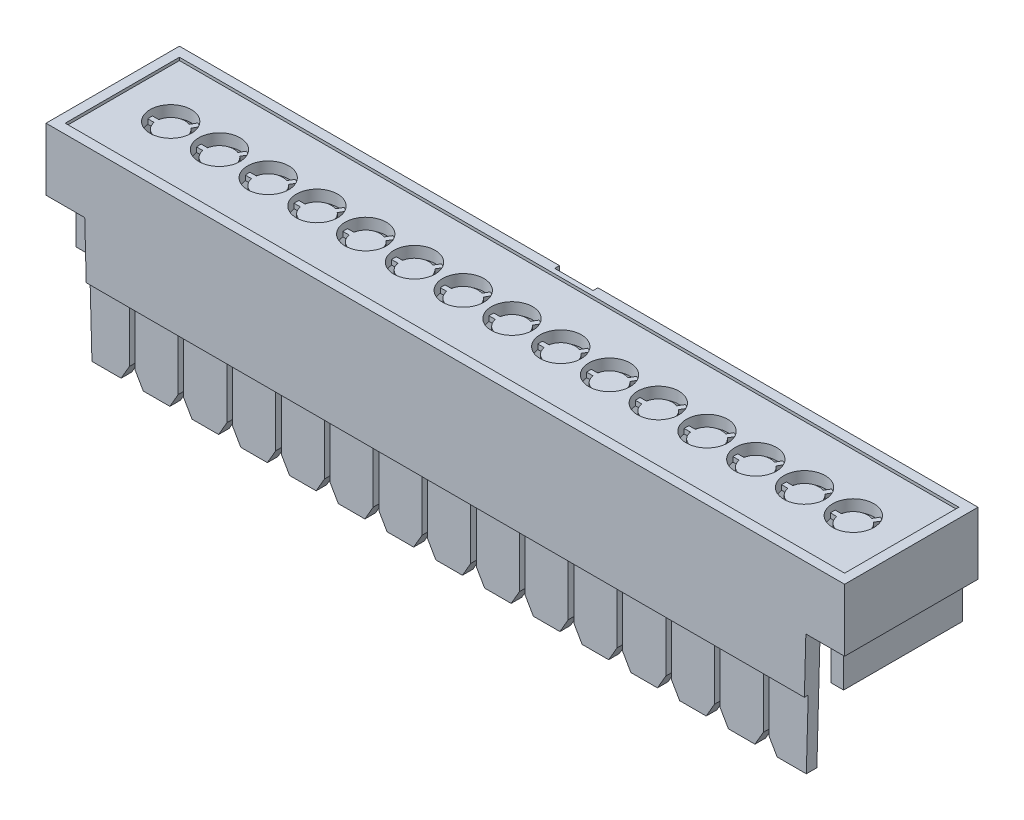
SolidWorks part; units mm, degrees
ref_plane "Спереди" through (0, 0, 0) normal (0, 0, 1) x (1, 0, 0)
ref_plane "Сверху" through (0, 0, 0) normal (0, 1, 0) x (1, 0, 0)
ref_plane "Справа" through (0, 0, 0) normal (1, 0, 0) x (0, 0, -1)
sketch "Эскиз1" plane through (0, 0, 0) normal (0, 1, 0) x (1, 0, 0)
  line L1 (41.6, -6.95) -> (-41.6, -6.95)
  line L2 (41.6, -6.95) -> (41.6, 6.95)
  line L3 (41.6, 6.95) -> (-41.6, 6.95)
  line L4 (-41.6, -6.95) -> (-41.6, 6.95)
  line L5 (41.6, -6.95) -> (-41.6, 6.95) construction
  line L6 (41.6, 6.95) -> (-41.6, -6.95) construction
  point P0 (0, 0)
  dimension "D1" = 13.9
  dimension "D2" = 83.2
extrude "Бобышка-Вытянуть1" add sketch "Эскиз1" against normal blind 6.5
sketch "Эскиз2" plane through (0, -6.5, 0) normal (0, -1, 0) x (1, 0, 0)
  line L0 (-41.6, 6.95) -> (41.6, 6.95) construction
  line L1 (38.7, -5.45) -> (-38.7, -5.45)
  line L2 (38.7, -5.45) -> (38.7, 5.45)
  line L3 (38.7, 5.45) -> (-38.7, 5.45)
  line L4 (-38.7, -5.45) -> (-38.7, 5.45)
  line L5 (38.7, -5.45) -> (-38.7, 5.45) construction
  line L6 (38.7, 5.45) -> (-38.7, -5.45) construction
  line L7 (-41.6, -6.95) -> (-41.6, 6.95) construction
  point P0 (0, 0)
  dimension "D1" = 1.5
  dimension "D2" = 2.9
extrude "Вырез-Вытянуть1" cut sketch "Эскиз2" against normal blind 5
sketch "Эскиз3" plane through (0, -6.5, 0) normal (0, -1, 0) x (1, 0, 0)
  line L0 (-38.7, 5.45) -> (-40, 5.45)
  line L1 (-40, 5.45) -> (-40, -6.95)
  line L2 (41.6, -6.95) -> (-41.6, -6.95) construction
  line L3 (-40, -6.95) -> (40, -6.95)
  line L4 (40, -6.95) -> (40, 5.45)
  line L5 (40, 5.45) -> (38.7, 5.45)
  line L6 (38.7, 5.45) -> (38.7, -5.45)
  line L7 (38.7, -5.45) -> (-38.7, -5.45)
  line L8 (-38.7, -5.45) -> (-38.7, 5.45)
  line L9 (0, 6.95) -> (0, -6.95) construction
  line L10 (-41.6, 6.95) -> (41.6, 6.95) construction
  dimension "D1" = 1.3
extrude "Бобышка-Вытянуть2" add sketch "Эскиз3" along normal blind 4.6
sketch "Эскиз4" plane through (0, 0, -6.95) normal (0, 0, -1) x (-1, 0, 0)
  line L0 (0, 0) -> (0, -11.1) construction
  line L1 (40, -11.1) -> (-40, -11.1) construction
  line L2 (-38.7, -11.1) -> (-38.7, -1.5)
  line L3 (-38.7, -1.5) -> (-37.7, -1.5)
  line L4 (-37.7, -1.5) -> (-37.4673, -10.1)
  line L5 (-37.4673, -10.1) -> (37.4673, -10.1)
  line L6 (37.4673, -10.1) -> (37.7, -1.5)
  line L7 (37.7, -1.5) -> (38.7, -1.5)
  line L8 (38.7, -1.5) -> (38.7, -11.1)
  line L9 (38.7, -11.1) -> (-38.7, -11.1)
  line L10 (-38.7, -11.1) -> (-38.7, -6.5) construction
  line L11 (-41.6, 0) -> (41.6, 0) construction
  dimension "D1" = 1
  dimension "D2" = 1
  dimension "D3" = 91.55
  dimension "D4" = 1.5
extrude "Вырез-Вытянуть2" cut sketch "Эскиз4" against normal up to surface (1.5 mm away) up to face at (0, -6.3, -5.45)
sketch "Эскиз5" plane through (0, 0, 0) normal (0, 1, 0) x (1, 0, 0)
  line L0 (0, 0) -> (0, 6.95) construction
  line L1 (41.6, 6.95) -> (-41.6, 6.95) construction
  line L3 (-2, 6.95) -> (2, 6.95)
  line L4 (-2, 6.95) -> (-2, 6.45)
  line L5 (-2, 6.45) -> (2, 6.45)
  line L6 (2, 6.95) -> (2, 6.45)
  dimension "D1" = 0.5
  dimension "D2" = 4
extrude "Вырез-Вытянуть3" cut sketch "Эскиз5" against normal blind 6.5
sketch "Эскиз6" plane through (0, 0, 0) normal (1, 0, 0) x (0, 0, -1)
  line L0 (6.95, -6.5) -> (7.95, -6.5)
  line L1 (7.95, -6.5) -> (6.95, -8.9)
  line L2 (6.95, -11.1) -> (6.95, -6.5) construction
  line L3 (6.95, -8.9) -> (6.95, -6.5)
  dimension "D1" = 2.4
  dimension "D2" = 1
extrude "Бобышка-Вытянуть3" add sketch "Эскиз6" along normal mid plane 3
sketch "Эскиз7" plane through (0, 0, 6.95) normal (0, 0, 1) x (1, 0, 0)
  line L0 (-37.5647, -6.5) -> (37.5647, -6.5)
  line L1 (-41.6, -6.5) -> (41.6, -6.5) construction
  line L2 (37.5647, -6.5) -> (37.4078, -12.3)
  line L3 (37.4078, -12.3) -> (-37.4078, -12.3)
  line L4 (-37.4078, -12.3) -> (-37.5647, -6.5)
  line L5 (-37.4673, -10.1) -> (-37.7, -1.5) construction
  line L6 (37.7, -1.5) -> (37.4673, -10.1) construction
  dimension "D1" = 5.8
extrude "Бобышка-Вытянуть4" add sketch "Эскиз7" against normal up to surface (1.5 mm away) up to face at (0, -4, 5.45)
sketch "Эскиз8" plane through (0, 0, 5.45) normal (0, 0, -1) x (-1, 0, 0)
  line L0 (0, 0) -> (0, -12.3) construction
  line L1 (-37.4078, -12.3) -> (37.4078, -12.3) construction
  line L2 (-37.4078, -12.3) -> (-37.2129, -19.5)
  line L3 (-37.2129, -19.5) -> (-34.176, -19.5)
  line L4 (-34.176, -19.5) -> (-33.31, -18)
  line L5 (-33.31, -18) -> (-33.31, -12.3)
  line L6 (37.4078, -12.3) -> (37.2129, -19.5)
  line L7 (37.2129, -19.5) -> (34.176, -19.5)
  line L8 (34.176, -19.5) -> (33.31, -18)
  line L9 (33.31, -18) -> (33.31, -12.3)
  line L10 (-37.4078, -12.3) -> (37.4078, -12.3)
  line L11 (-37.5647, -6.5) -> (-37.4078, -12.3) construction
  line L12 (-2.25, -12.3) -> (-2.25, -18)
  line L13 (-2.25, -18) -> (-1.384, -19.5)
  line L14 (-1.384, -19.5) -> (1.384, -19.5)
  line L15 (1.384, -19.5) -> (2.25, -18)
  line L16 (2.25, -18) -> (2.25, -12.3)
  line L17 (2.83, -12.3) -> (2.83, -18)
  line L18 (2.83, -18) -> (3.696, -19.5)
  line L19 (3.696, -19.5) -> (6.464, -19.5)
  line L20 (6.464, -19.5) -> (7.33, -18)
  line L21 (7.33, -18) -> (7.33, -12.3)
  line L22 (7.91, -12.3) -> (7.91, -18)
  line L23 (7.91, -18) -> (8.776, -19.5)
  line L24 (8.776, -19.5) -> (11.544, -19.5)
  line L25 (11.544, -19.5) -> (12.41, -18)
  line L26 (12.41, -18) -> (12.41, -12.3)
  line L27 (12.99, -12.3) -> (12.99, -18)
  line L28 (12.99, -18) -> (13.856, -19.5)
  line L29 (13.856, -19.5) -> (16.624, -19.5)
  line L30 (16.624, -19.5) -> (17.49, -18)
  line L31 (17.49, -18) -> (17.49, -12.3)
  line L32 (18.07, -12.3) -> (18.07, -18)
  line L33 (18.07, -18) -> (18.936, -19.5)
  line L34 (18.936, -19.5) -> (21.704, -19.5)
  line L35 (21.704, -19.5) -> (22.57, -18)
  line L36 (22.57, -18) -> (22.57, -12.3)
  line L37 (23.15, -12.3) -> (23.15, -18)
  line L38 (23.15, -18) -> (24.016, -19.5)
  line L39 (24.016, -19.5) -> (26.784, -19.5)
  line L40 (26.784, -19.5) -> (27.65, -18)
  line L41 (27.65, -18) -> (27.65, -12.3)
  line L42 (28.23, -12.3) -> (28.23, -18)
  line L43 (28.23, -18) -> (29.096, -19.5)
  line L44 (29.096, -19.5) -> (31.864, -19.5)
  line L45 (31.864, -19.5) -> (32.73, -18)
  line L46 (32.73, -18) -> (32.73, -12.3)
  line L47 (-7.33, -12.3) -> (-7.33, -18)
  line L48 (-7.33, -18) -> (-6.464, -19.5)
  line L49 (-6.464, -19.5) -> (-3.696, -19.5)
  line L50 (-3.696, -19.5) -> (-2.83, -18)
  line L51 (-2.83, -18) -> (-2.83, -12.3)
  line L52 (-12.41, -12.3) -> (-12.41, -18)
  line L53 (-12.41, -18) -> (-11.544, -19.5)
  line L54 (-11.544, -19.5) -> (-8.776, -19.5)
  line L55 (-8.776, -19.5) -> (-7.91, -18)
  line L56 (-7.91, -18) -> (-7.91, -12.3)
  line L57 (-17.49, -12.3) -> (-17.49, -18)
  line L58 (-17.49, -18) -> (-16.624, -19.5)
  line L59 (-16.624, -19.5) -> (-13.856, -19.5)
  line L60 (-13.856, -19.5) -> (-12.99, -18)
  line L61 (-12.99, -18) -> (-12.99, -12.3)
  line L62 (-22.57, -12.3) -> (-22.57, -18)
  line L63 (-22.57, -18) -> (-21.704, -19.5)
  line L64 (-21.704, -19.5) -> (-18.936, -19.5)
  line L65 (-18.936, -19.5) -> (-18.07, -18)
  line L66 (-18.07, -18) -> (-18.07, -12.3)
  line L67 (-27.65, -12.3) -> (-27.65, -18)
  line L68 (-27.65, -18) -> (-26.784, -19.5)
  line L69 (-26.784, -19.5) -> (-24.016, -19.5)
  line L70 (-24.016, -19.5) -> (-23.15, -18)
  line L71 (-23.15, -18) -> (-23.15, -12.3)
  line L72 (-32.73, -12.3) -> (-32.73, -18)
  line L73 (-32.73, -18) -> (-31.864, -19.5)
  line L74 (-31.864, -19.5) -> (-29.096, -19.5)
  line L75 (-29.096, -19.5) -> (-28.23, -18)
  line L76 (-28.23, -18) -> (-28.23, -12.3)
  point P19 (33.3459, -18)
  line M49 (-37.4078, -12.3) -> (37.4078, -12.3)
  dimension "D1" = 7.2
  dimension "D2" = 4.5
  dimension "D3" = 30
  dimension "D4" = 1.5
  dimension "D6" = 5.08
  dimension "D7" = 5.08
  dimension "D9" = 0.58
  dimension "D5" = 7
  dimension "D8" = 7
extrude "Бобышка-Вытянуть5" add sketch "Эскиз8" against normal blind 1.1 contours L9 L8 L7 L6 M49 | L45 L46 L10 L42 L43 L44 | L40 L41 L10 L37 L38 L39 | L35 L36 L10 L32 L33 L34 | L30 L31 L10 L27 L28 L29 | L25 L26 L10 L22 L23 L24 | L20 L21 L10 L17 L18 L19 | L15 L16 L10 L12 L13 L14 M49 | L50 L51 L10 L47 L48 L49 | L55 L56 L10 L52 L53 L54 | L60 L61 L10 L57 L58 L59 | L65 L66 L10 L62 L63 L64 | L70 L71 L10 L67 L68 L69 | L75 L76 L10 L72 L73 L74 | L4 L5 L2 L3 M49 region at (35.3501, -15.7986, 5.45) region at (-35.3501, -15.7986, 5.45) region at (-30.48, -15.7705, 5.45) region at (-25.4, -15.7705, 5.45) region at (-20.32, -15.7705, 5.45) region at (-15.24, -15.7705, 5.45) region at (-10.16, -15.7705, 5.45) region at (-5.08, -15.7705, 5.45) region at (0, -15.7705, 5.45) region at (5.08, -15.7705, 5.45) region at (10.16, -15.7705, 5.45) region at (15.24, -15.7705, 5.45) region at (20.32, -15.7705, 5.45) region at (25.4, -15.7705, 5.45) region at (30.48, -15.7705, 5.45)
sketch "Эскиз9" plane through (0, 0, 0) normal (0, 1, 0) x (1, 0, 0)
  line L0 (-41.6, 6.95) -> (-41.6, -6.95) construction
  line L1 (40.6, -5.95) -> (-40.6, -5.95)
  line L2 (40.6, -5.95) -> (40.6, 5.95)
  line L3 (40.6, 5.95) -> (-40.6, 5.95)
  line L4 (-40.6, -5.95) -> (-40.6, 5.95)
  line L5 (40.6, -5.95) -> (-40.6, 5.95) construction
  line L6 (40.6, 5.95) -> (-40.6, -5.95) construction
  line L7 (-2, 6.95) -> (-41.6, 6.95) construction
  point P0 (0, 0)
  dimension "D1" = 1
  dimension "D2" = 1
extrude "Вырез-Вытянуть4" cut sketch "Эскиз9" against normal blind 0.3
sketch "Эскиз10" plane through (0, -0.3, 0) normal (0, 1, 0) x (1, 0, 0)
  circle A0 centre (0, 0) radius 2.15
  dimension "D1" = 4.3
extrude "Вырез-Вытянуть5" cut sketch "Эскиз10" against normal blind 0.7
sketch "Эскиз11" plane through (0, -1, 0) normal (0, 1, 0) x (1, 0, 0)
  line L0 (-1.479, 0.25) -> (-2.1354, 0.25)
  line L1 (-2.1354, -0.25) -> (-1.479, -0.25)
  line L2 (0.523, 1.4059) -> (0.8512, 1.9743)
  line L3 (0.956, 1.1559) -> (1.2842, 1.7243)
  line L4 (0.956, -1.1559) -> (1.2842, -1.7243)
  line L5 (0.8512, -1.9743) -> (0.523, -1.4059)
  line L6 (0, 0) -> (-2.15, 0) construction
  line L7 (0, 0) -> (1.075, 1.862) construction
  circle A0 centre (0, 0) radius 1.5
  circle A1 centre (0, 0) radius 2.15 construction
  arc A2 (-2.1354, 0.25) -> (0.8512, 1.9743) centre (0, 0) cw
  arc A3 (-2.1354, -0.25) -> (0.8512, -1.9743) centre (0, 0) ccw
  arc A4 (1.2842, -1.7243) -> (1.2842, 1.7243) centre (0, 0) ccw
  circle M9 centre (0, 0) radius 2.15
  dimension "D1" = 3
  dimension "D2" = 0.5
  dimension "D3" = 0.5
  dimension "D4" = 0.5
  dimension "D7" = 120
extrude "Вырез-Вытянуть6" cut sketch "Эскиз11" against normal up to surface (0.5 mm away) contours A0 L2 L0 M9 | A0 L1 L5 M9 | A0 L4 L3 M9 region at (-0.8009, -1, -1.3872) region at (-0.8009, -1, 1.3872) region at (1.6018, -1, 0) up to face at (0, -1.5, -3.475)
pattern_linear "Линейный массив1" count 8 spacing 5.08 along (-1, 0, 0) count 8 spacing 5.08 along (1, 0, 0) of "Вырез-Вытянуть5", "Вырез-Вытянуть6"
